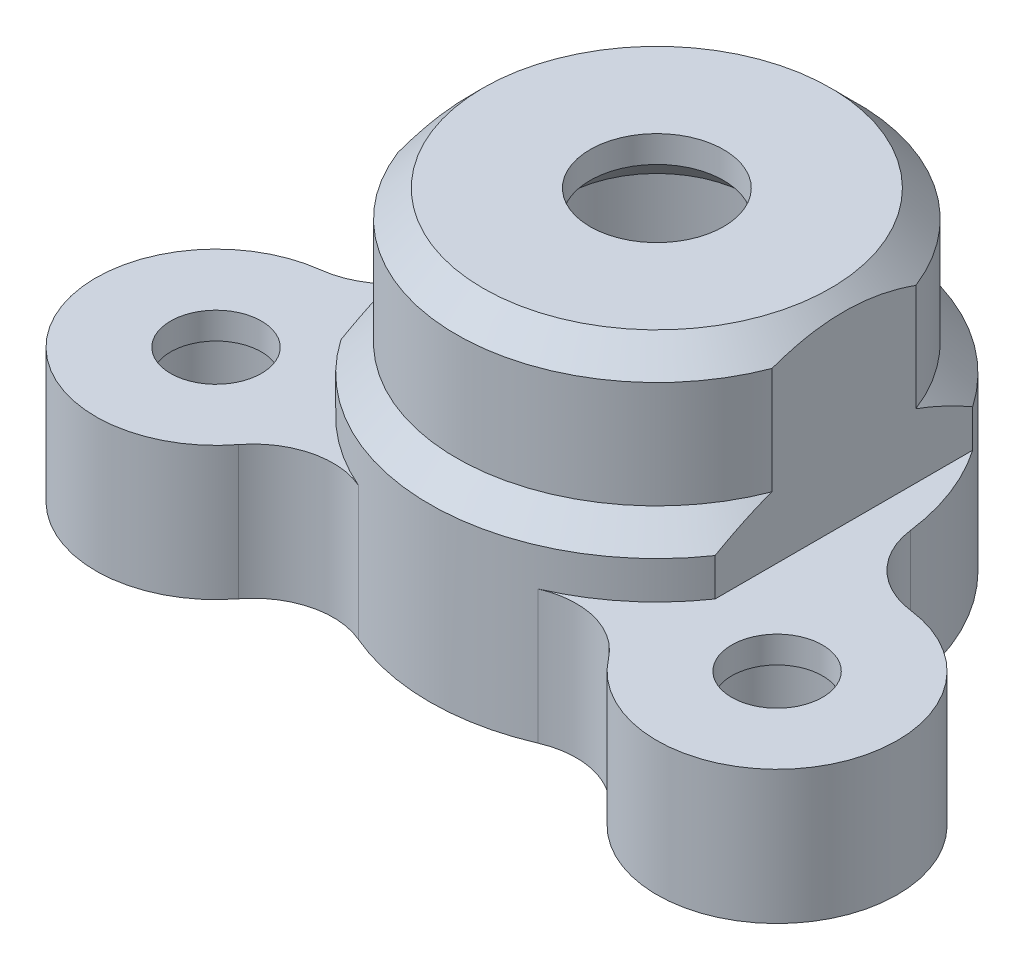
SolidWorks part; units mm, degrees
ref_plane "Plan de face" through (0, 0, 0) normal (0, 0, 1) x (1, 0, 0)
ref_plane "Plan de dessus" through (0, 0, 0) normal (0, 1, 0) x (1, 0, 0)
ref_plane "Plan de droite" through (0, 0, 0) normal (1, 0, 0) x (0, 0, -1)
sketch "Esquisse1" plane through (0, 0, 0) normal (0, 1, 0) x (1, 0, 0)
  line L0 (0, 8.5) -> (0, -8.5) construction
  line L1 (0, 0) -> (-7.3612, 4.25) construction
  line L2 (0, 0) -> (7.3612, 4.25) construction
  line L3 (-10.5, -1.5) -> (-6.3246, -1.5)
  line L4 (10.5, -1.5) -> (6.3246, -1.5)
  circle A0 centre (0, 0) radius 5.5 construction
  circle A2 centre (-10.5, -6) radius 1.7 construction
  arc A3 (-6, -6.0207) -> (6, -6.0207) centre (0, 0) ccw
  circle A4 centre (-10.5, -6) radius 2.5
  arc A5 (-10.5, -1.5) -> (-6, -6.0207) centre (-10.5, -6) ccw
  circle A6 centre (0, 0) radius 6.5
  circle A8 centre (10.5, -6) radius 1.7 construction
  circle A10 centre (10.5, -6) radius 2.5
  arc A11 (10.5, -1.5) -> (6, -6.0207) centre (10.5, -6) cw
  arc A12 (8.3666, -1.5) -> (-8.3666, -1.5) centre (0, 0) ccw construction
  dimension "D1" = 11
  dimension "D4" = 3.4
  dimension "D5" = 2
  dimension "D6" = 3
  dimension "D7" = 5
  dimension "D9" = 1
  dimension "D2" = 10.5
  dimension "D3" = 6
  dimension "D10" = 60
  dimension "D11" = 60
sketch "Esquisse2" plane through (0, 0, 0) normal (0, 0, 1) x (1, 0, 0)
  line L0 (0, 9) -> (0, 0) construction
  line L1 (-2.5, 9) -> (-2.5, 8)
  line L2 (-2.5, 8) -> (-3.5, 7)
  line L3 (-3.5, 7) -> (-5.5, 7)
  line L4 (-5.5, 7) -> (-5.5, 3)
  line L5 (-5.5, 3) -> (-6.5, 2)
  line L7 (-8.5, 0) -> (-8.5, 3)
  line L8 (-8.5, 9) -> (-2.5, 9) construction
  line L9 (-6.5, 2) -> (-6.5, 0)
  line L10 (-8.5, 3) -> (-7.5, 4)
  line L11 (-6.5, 0) -> (-8.5, 0)
  line L12 (-7.5, 4) -> (-7.5, 8)
  line L13 (-8.5, 3) -> (-8.5, 9) construction
  line L14 (-6.5, 9) -> (-2.5, 9)
  line L15 (-7.5, 8) -> (-6.5, 9)
  point P13 (-2.5, 10.4074)
  point P16 (0, 0)
  point P17 (0, 0)
  point P18 (-4.8984, 9)
  point P19 (0, 0)
  point P22 (-11.6793, 9)
  point P23 (-2.4088, 9)
  dimension "D1" = 2.5
  dimension "D2" = 5.5
  dimension "D3" = 2
  dimension "D4" = 1
  dimension "D5" = 1
  dimension "D6" = 4
  dimension "D7" = 1
  dimension "D8" = 8.5
  dimension "D9" = 2
  dimension "D10" = 1
  dimension "D11" = 1
revolve "Révolution1" add sketch "Esquisse2" angle 360 about L0
extrude "Boss.-Extru.1" add sketch "Esquisse1" against normal blind 5 from offset 1.5917 contours A11 A6 A5 A3 A4 A10 | A4 | A10 region at (-8.4123, 0, 1.8132) region at (-10.5, 0, 6) region at (10.5, 0, 6)
extrude "Enlèv. mat.-Extru.3" cut sketch "Esquisse1<7>" along normal blind 4 from surface contours A4 | A10 region at (-10.5, 0, 6) region at (10.5, 0, 6) starting at face at (0, -3.4082, 6.0582)
sketch "Esquisse1<7>" plane through (0, 0, 0) normal (0, 1, 0) x (1, 0, 0) same geometry as "Esquisse1"
sketch "Esquisse9" plane through (0, -3.4082, 0) normal (0, -1, 0) x (-1, 0, 0)
  point P0 (-10.5, -6)
  point P3 (10.5, -6)
hole_wizard "M3 Clearance Hole2" positions "Esquisse9" profile "Esquisse8" hole size "M3" standard "ANSI Metric" end condition up to next
sketch "Esquisse8" plane through (10.5, -3.4082, 6) normal (1, 0, 0) x (0, 0, -1)
  line L0 (0, 0) -> (0, 5)
  line L1 (0, 5) -> (1.7, 5)
  line L2 (1.7, 5) -> (1.7, 0)
  line L5 (1.7, 0) -> (0, 0)
  line L11 (0, -6.35) -> (0, 107.95) construction
  dimension "Thru Hole Dia." = 3.4
  dimension "Thru Hole Depth" = 5
sketch "Esquisse10" plane through (0, -3.4082, 0) normal (0, -1, 0) x (1, 0, 0)
  line L3 (10.5, 1.5) -> (6.3246, 1.5) construction
  line L4 (8.3666, 1.5) -> (6.3246, 1.5) construction
  line L5 (6.3246, 1.5) -> (8.3666, 1.5)
  line L6 (-6.3246, 1.5) -> (-8.3666, 1.5)
  arc A1 (-8.3666, 1.5) -> (8.3666, 1.5) centre (0, 0) ccw
  arc A2 (-6.3246, 1.5) -> (6.3246, 1.5) centre (0, 0) ccw
  line M19 (-10.5, 1.5) -> (-6.3246, 1.5)
  line M21 (6.3246, 1.5) -> (10.5, 1.5)
extrude "Boss.-Extru.3" add sketch "Esquisse10" along normal up to surface from surface contours A2 A1 M19 | A2 A1 | A2 A1 M21 region at (7.3456, -3.4082, 1.3028) up to face at (-10.5, -3.4082, 8.5) starting at face at (0, 0, -3)
sketch "Esquisse11" plane through (0, 9, 0) normal (0, 1, 0) x (1, 0, 0)
  line L0 (-7, 4.8218) -> (-7, -4.8218)
  line L1 (7, 4.8218) -> (7, -4.8218)
  circle A0 centre (0, 0) radius 8.5 construction
  arc A1 (-8.3666, -1.5) -> (-6, -6.0207) centre (0, 0) ccw construction
  arc A2 (-7, -4.8218) -> (-7, 4.8218) centre (0, 0) cw
  arc A3 (7, 4.8218) -> (7, -4.8218) centre (0, 0) cw
  dimension "D1" = 14
extrude "Enlèv. mat.-Extru.5" cut sketch "Esquisse11" against normal up to surface (7.4082 mm away) contours A2 L0 | A3 L1 region at (-7.6048, 9, 0) region at (7.6048, 9, 0) up to face at (-10.5, 1.5918, 7.7)
fillet "Congé5" radius 3 4 edges at (-8.3666, -0.9082, 1.5) (8.3666, -0.9083, 1.5) (6, -0.9082, 6.0207) (-6, -0.9082, 6.0207)
chamfer "Chanfrein5" distance 0.5 angle 45 2 edges at (-10.5, -3.4082, 8.5) (10.5, -3.4082, 8.5)
